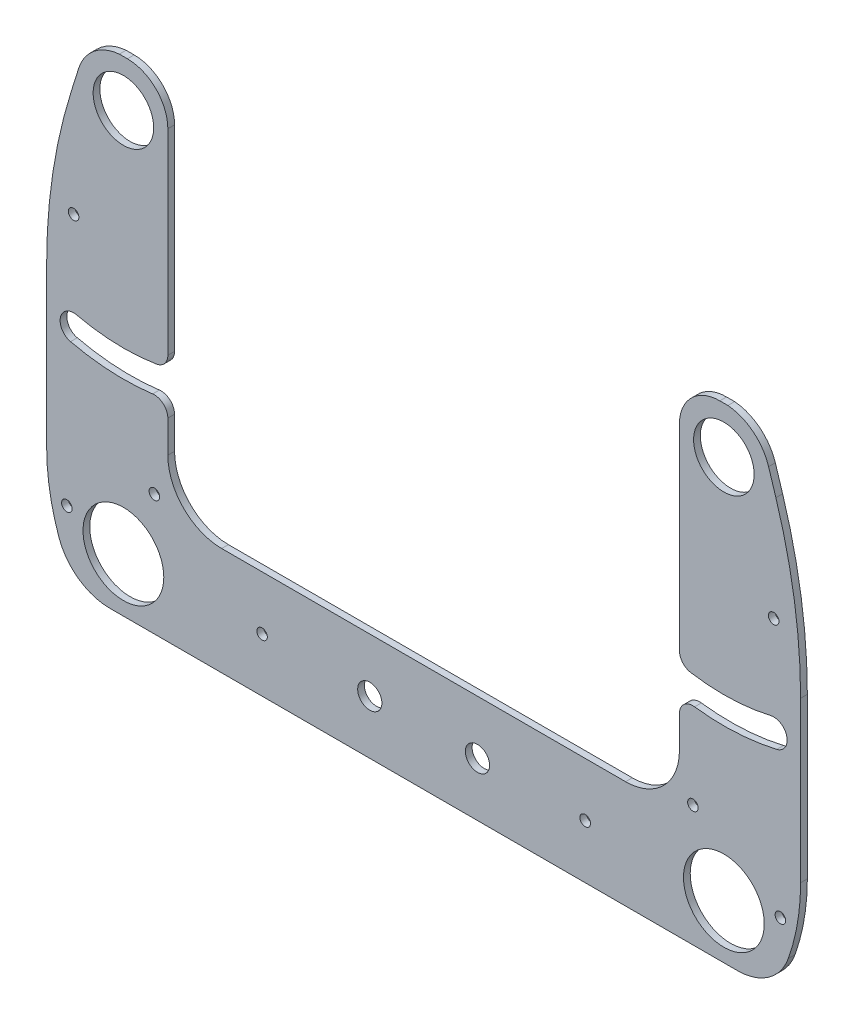
SolidWorks part; units mm, degrees
material "6061 Alloy"
ref_plane "Front Plane" through (0, 0, 0) normal (0, 0, 1) x (1, 0, 0)
ref_plane "Top Plane" through (0, 0, 0) normal (0, 1, 0) x (1, 0, 0)
ref_plane "Right Plane" through (0, 0, 0) normal (1, 0, 0) x (0, 0, -1)
sketch "Sketch1" plane through (0, 0, 0) normal (0, 0, 1) x (1, 0, 0)
  line L5 (120.65, -152.4) -> (120.65, -6.35)
  line L6 (127, 0) -> (171.45, 0) construction
  line L7 (177.8, -6.35) -> (177.8, -222.25)
  line L10 (0, -206.2199) -> (0, -63.6275) construction
  line L11 (-54.9244, 0) -> (300.6756, 0) construction
  line L13 (12.7, -177.8) -> (95.25, -177.8)
  line L14 (12.7, -228.6) -> (171.45, -228.6)
  line L15 (141.605, -22.0269) -> (141.605, -80.9091) construction
  line L16 (141.605, -22.0269) -> (141.605, -123.6269) construction
  line L19 (-141.605, -19.05) -> (-141.605, -77.9322) construction
  line L20 (141.605, -22.0269) -> (141.605, -203.2) construction
  line L22 (-120.65, -152.4) -> (-120.65, -6.35)
  line L23 (-12.7, -177.8) -> (-95.25, -177.8)
  line L24 (-12.7, -228.6) -> (-171.45, -228.6)
  line L25 (-177.8, -6.35) -> (-177.8, -222.25)
  line L26 (-12.7, -177.8) -> (12.7, -177.8)
  line L27 (-12.7, -228.6) -> (12.7, -228.6)
  line L28 (-177.8, -6.35) -> (-177.8, 6.35)
  line L29 (-165.1, 19.05) -> (-133.35, 19.05)
  line L30 (-120.65, 6.35) -> (-120.65, -6.35)
  line L31 (120.65, 6.35) -> (120.65, -6.35)
  line L32 (177.8, -6.35) -> (177.8, 6.35)
  line L33 (165.1, 19.05) -> (133.35, 19.05)
  arc A0 (95.25, -177.8) -> (120.65, -152.4) centre (95.25, -152.4) ccw
  arc A4 (120.65, -6.35) -> (127, 0) centre (127, -6.35) cw construction
  circle A8 centre (141.605, -22.0269) radius 14.2875
  circle A9 centre (141.605, -22.0269) radius 38.1 construction
  arc A10 (177.8, -6.35) -> (171.45, 0) centre (171.45, -6.35) ccw construction
  arc A11 (171.45, -228.6) -> (177.8, -222.25) centre (171.45, -222.25) ccw
  arc A14 (141.605, -79.1769) -> (120.9214, -75.3027) centre (141.605, -22.0269) ccw construction
  arc A15 (-141.605, -79.1769) -> (-120.9214, -75.3027) centre (-141.605, -22.0269) cw construction
  circle A16 centre (-141.605, -22.0269) radius 38.1 construction
  circle A17 centre (-141.605, -22.0269) radius 14.2875
  arc A19 (-95.25, -177.8) -> (-120.65, -152.4) centre (-95.25, -152.4) cw
  circle A20 centre (141.605, -123.6269) radius 38.1 construction
  circle A21 centre (-141.605, -123.6269) radius 38.1 construction
  arc A23 (-171.45, -228.6) -> (-177.8, -222.25) centre (-171.45, -222.25) cw
  circle A24 centre (-141.605, -203.2) radius 19.05
  circle A37 centre (141.605, -203.2) radius 19.05
  circle A39 centre (-76.2, -203.2) radius 2.4892
  circle A40 centre (76.2, -203.2) radius 2.4892
  circle A42 centre (-25.4, -203.2) radius 5.715
  arc A44 (-133.35, 19.05) -> (-120.65, 6.35) centre (-133.35, 6.35) cw
  arc A45 (-177.8, 6.35) -> (-165.1, 19.05) centre (-165.1, 6.35) cw
  arc A46 (133.35, 19.05) -> (120.65, 6.35) centre (133.35, 6.35) ccw
  arc A47 (177.8, 6.35) -> (165.1, 19.05) centre (165.1, 6.35) ccw
  circle A50 centre (-149.225, 6.35) radius 2.4892
  circle A53 centre (149.225, 6.35) radius 2.4892
  circle A54 centre (-168.275, -196.85) radius 2.4892
  circle A56 centre (168.275, -196.85) radius 2.4892
  circle A58 centre (-165.1, -76.2) radius 2.4892
  circle A59 centre (165.1, -76.2) radius 2.4892
  circle A60 centre (-127, -171.45) radius 2.4892
  circle A61 centre (127, -171.45) radius 2.4892
  circle A62 centre (25.4, -203.2) radius 5.715
  point P2 (177.8, -44.45)
  point P18 (177.8, 0)
  point P23 (177.8, -228.6)
  point P24 (177.8, -228.6)
  point P31 (177.8, 0)
  point P48 (-177.8, 0)
  point P49 (-177.8, -228.6)
  point P51 (-177.8, -44.45)
  point P78 (-141.605, -203.2)
  dimension "D6" = 25.4
  dimension "D7" = 6.35
  dimension "D8" = 6.35
  dimension "D9" = 177.8
  dimension "D10" = 28.575
  dimension "D12" = 76.2
  dimension "D13" = 57.15
  dimension "D15" = 38.1
  dimension "D18" = 76.2
  dimension "D21" = 4.9784
  dimension "D29" = 9.525
  dimension "D32" = 4.9784
  dimension "D35" = 11.43
  dimension "D40" = 12.7
  dimension "D43" = 4.9784
  dimension "D45" = 12.7
  dimension "D30" = 4.9784
  dimension "D41" = 4.9784
  dimension "D22" = 6.35
  dimension "D2" = 120.65
  dimension "D3" = 177.8
  dimension "D4" = 228.6
  dimension "D5" = 177.8
  dimension "D11" = 20.955
  dimension "`" = 22.0269
  dimension "D14" = 57.15
  dimension "D16" = 184.15
  dimension "D17" = 101.6
  dimension "D19" = 25.4
  dimension "D20" = 101.6
  dimension "D23" = 57.15
  dimension "D25" = 25.4
  dimension "D26" = 31.75
  dimension "D27" = 25.4
  dimension "D28" = 25.4
  dimension "D31" = 25.4
  dimension "D33" = 12.7
  dimension "D34" = 25.4
  dimension "D39" = 19.05
  dimension "D44" = 28.575
  dimension "D24" = 95.25
extrude "Boss-Extrude3" add sketch "Sketch1" along normal blind 3.175
sketch "Sketch2" plane through (0, 0, 3.175) normal (0, 0, 1) x (1, 0, 0)
  line L0 (177.8, -222.25) -> (177.8, 6.35) construction
  line L1 (-177.8, 19.05) -> (177.8, 19.05)
  line L2 (-177.8, 19.05) -> (-177.8, 0)
  line L3 (-177.8, 0) -> (177.8, 0)
  line L4 (177.8, 19.05) -> (177.8, 0)
  line L5 (-177.8, 6.35) -> (-177.8, -222.25) construction
  line L7 (-133.35, 19.05) -> (-165.1, 19.05) construction
  dimension "D1" = 19.05
extrude "Cut-Extrude1" cut sketch "Sketch2" against normal through all
fillet "Fillet1" radius 19.05 4 edges at (177.8, 0, 1.5875) (120.65, 0, 1.5875) (-120.65, 0, 1.5875) (-177.8, 0, 1.5875)
sketch "Sketch3" plane through (0, 0, 3.175) normal (0, 0, 1) x (1, 0, 0)
  line L2 (-177.8, -19.05) -> (-177.8, -222.25) construction
  line L3 (-158.75, 0) -> (-139.7, 0) construction
  line L4 (-177.8, -63.5) -> (-177.8, 0)
  line L5 (-177.8, 0) -> (-139.7, 0)
  line L6 (-177.8, -63.5) -> (-162.6988, -15.4039)
  arc A3 (-139.7, 0) -> (-162.6988, -15.4039) centre (-141.605, -22.0269) ccw
  arc M14 (-158.75, 0) -> (-177.8, -19.05) centre (-158.75, -19.05) ccw
  line M15 (-177.8, -19.05) -> (-177.8, -222.25)
  dimension "D1" = 63.5
extrude "Cut-Extrude2" cut sketch "Sketch3" against normal through all contours A3 L5 M14 M15 | L5 L4 M14 region at (-169.5998, -21.9282, 3.175) region at (-173.5448, -4.2552, 3.175)
ref_plane "Plane1" through (0, 0, 0) normal (-1, 0, 0) x (0, 0, 1)
mirror "Mirror1" about plane through (0, 0, 0) normal (-1, 0, 0) of "Cut-Extrude2"
fillet "Fillet2" radius 254 2 edges at (177.8, -63.5, 1.5875) (-177.8, -63.5, 1.5875)
sketch "Sketch4" plane through (0, 0, 3.175) normal (0, 0, 1) x (1, 0, 0)
  line L0 (0, -177.8) -> (0, -13.685) construction
  line L5 (-177.8, -102.4383) -> (-177.8, -222.25) construction
  line L6 (-171.45, -228.6) -> (171.45, -228.6) construction
  line L7 (-177.8, -177.8) -> (-177.8, -228.6)
  line L8 (-177.8, -228.6) -> (-164.1882, -228.6)
  line L9 (177.8, -177.8) -> (177.8, -228.6)
  line L10 (177.8, -228.6) -> (164.1882, -228.6)
  circle A0 centre (-76.2, -177.8) radius 101.6 construction
  arc A1 (-177.8, -177.8) -> (-164.1882, -228.6) centre (-76.2, -177.8) ccw
  arc A2 (177.8, -177.8) -> (164.1882, -228.6) centre (76.2, -177.8) cw
  dimension "D1" = 203.2
  dimension "D2" = 50.8
extrude "Cut-Extrude3" cut sketch "Sketch4" against normal through all contours L8 A1 L7 | L9 L10 A2
fillet "Fillet3" radius 25.4 2 edges at (164.1882, -228.6, 1.5875) (-164.1882, -228.6, 1.5875)
sketch "Sketch5" plane through (0, 0, 3.175) normal (0, 0, 1) x (1, 0, 0)
  line L2 (-120.65, -129.7962) -> (-120.65, -116.8262)
  line L5 (120.65, -129.7962) -> (120.65, -116.8262)
  line L6 (120.65, -19.05) -> (120.65, -152.4) construction
  line L7 (177.8, -177.8) -> (177.8, -102.4383) construction
  line L8 (0, -203.7675) -> (0, -15.567) construction
  circle A4 centre (141.605, -22.0269) radius 103.4377 construction
  arc A5 (120.65, -116.8262) -> (163.6577, -116.5769) centre (141.605, -22.0269) ccw
  arc A6 (120.65, -129.7962) -> (166.5423, -128.9449) centre (141.605, -22.0269) ccw
  arc A9 (166.5423, -128.9449) -> (163.6577, -116.5769) centre (165.1, -122.7609) ccw
  arc A10 (-120.65, -129.7962) -> (-166.5423, -128.9449) centre (-141.605, -22.0269) cw
  arc A11 (-120.65, -116.8262) -> (-163.6577, -116.5769) centre (-141.605, -22.0269) cw
  arc A12 (-166.5423, -128.9449) -> (-163.6577, -116.5769) centre (-165.1, -122.7609) cw
  dimension "D1" = 97.0877
  dimension "D2" = 109.7877
  dimension "D4" = 12.7
  dimension "D3" = 206.8754
extrude "Cut-Extrude4" cut sketch "Sketch5" against normal through all contours A10 A12 A11 L2 | A9 A5 L5 A6
fillet "Fillet4" radius 6.35 4 edges at (120.65, -129.7962, 1.5875) (120.65, -116.8262, 1.5875) (-120.65, -129.7962, 1.5875) (-120.65, -116.8262, 1.5875)
sketch "Sketch6" plane through (0, 0, 0) normal (0, 0, -1) x (-1, 0, 0)
  line L0 (180.34, -1122.6748) -> (180.34, 48877.3252) construction
  line L1 (-743.0643, -231.14) -> (49256.9357, -231.14) construction
  line L3 (148.042, -228.6) -> (-148.042, -228.6) construction
  arc A1 (171.9894, -211.6667) -> (177.8, -177.8) centre (76.2, -177.8) ccw construction
  point P3 (180.34, -231.14)
  point P5 (0, 0)
  dimension "D2" = 104.14
  dimension "D1" = 2.54
